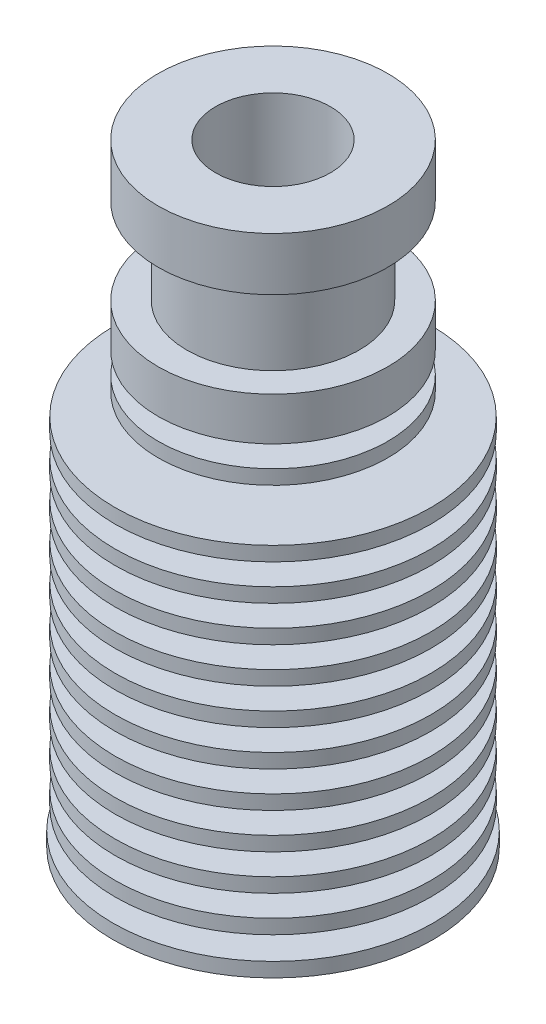
SolidWorks part; units mm, degrees
material "6061 Alloy"
ref_plane "Front Plane" through (0, 0, 0) normal (0, 0, 1) x (1, 0, 0)
ref_plane "Top Plane" through (0, 0, 0) normal (0, 1, 0) x (1, 0, 0)
ref_plane "Right Plane" through (0, 0, 0) normal (1, 0, 0) x (0, 0, -1)
sketch "Sketch1" plane through (0, 0, 0) normal (0, 0, 1) x (1, 0, 0)
  line L0 (0, 0) -> (0, -50000) construction
  line L1 (0, 0) -> (11.15, 0)
  line L2 (11.15, 0) -> (11.15, 1)
  line L3 (8, 30) -> (3.5, 30)
  line L4 (8, 30) -> (8, 33)
  line L5 (8, 33) -> (6, 33)
  line L6 (6, 33) -> (6, 39)
  line L7 (6, 39) -> (8, 39)
  line L8 (8, 39) -> (8, 42.7)
  line L9 (8, 42.7) -> (0, 42.7)
  line L10 (0, 42.7) -> (0, 0)
  line L12 (11, 1) -> (11, 26)
  line L13 (3.5, 26) -> (11, 26)
  line L14 (3.5, 27.5) -> (8, 27.5)
  line L15 (8, 27.5) -> (8, 28.5)
  line L16 (8, 28.5) -> (3.5, 28.5)
  line L17 (3.5, 28.5) -> (3.5, 30)
  line L18 (3.5, 27.5) -> (3.5, 26)
  line L20 (11.15, 1) -> (11, 1)
  dimension "D1" = 22.3
  dimension "D2" = 16
  dimension "D3" = 12
  dimension "D4" = 16
  dimension "D5" = 3.7
  dimension "D6" = 6
  dimension "D7" = 3
  dimension "D8" = 42.7
  dimension "D9" = 26
  dimension "D10" = 1.5
  dimension "D11" = 1
  dimension "D12" = 7
  dimension "D13" = 22
  dimension "D14" = 1
revolve "Revolve1" add sketch "Sketch1" angle 360 about L0 region at (4.9396, 19.0164, 0)
sketch "Sketch2" plane through (0, 0, 0) normal (0, 0, 1) x (1, 0, 0)
  line L0 (11, 1) -> (11, 26) construction
  line L3 (11, 1) -> (6, 1)
  line L4 (6, 1) -> (6, 2.5)
  line L5 (6, 2.5) -> (11, 2.5)
  line L6 (0, 0) -> (0, 26) construction
  line L7 (11.15, 26) -> (-11.15, 26) construction
  line L8 (11, 2.5) -> (11, 1)
  dimension "D1" = 2.5
  dimension "D3" = 12
revolve "Cut-Revolve1" cut sketch "Sketch2" angle 360 about L6 region at (8.5, 1.75, 0)
pattern_linear "LPattern1" count 10 spacing 2.5 along (0, 1, 0) of "Cut-Revolve1"
sketch "Sketch3" plane through (0, 0, 0) normal (0, 0, 1) x (1, 0, 0)
  line L0 (0, 42.7) -> (0, 0)
  line L1 (8, 42.7) -> (-8, 42.7) construction
  line L2 (0, 0) -> (2.1, 0)
  line L3 (-11.15, 0) -> (11.15, 0) construction
  line L4 (2.1, 0) -> (2.1, 34.3)
  line L6 (4, 36.2) -> (4, 42.7)
  line L7 (4, 42.7) -> (0, 42.7)
  line L8 (4, 36.2) -> (2.1, 34.3)
  dimension "D1" = 4
  dimension "D2" = 2.1
  dimension "D3" = 6.5
  dimension "D4" = 45
revolve "Cut-Revolve2" cut sketch "Sketch3" angle 360 about L0
hole_wizard "M7x1.0 Tapped Hole1" positions "Sketch5" profile "Sketch4" tap size "M7x1.0" standard "ANSI Metric"
sketch "Sketch5" plane through (0, 0, 0) normal (0, -1, 0) x (-1, 0, 0)
  point P0 (0, 0)
sketch "Sketch4" plane through (0, 0, 0) normal (1, 0, 0) x (0, 0, -1)
  line L0 (0, 0) -> (0, 16.9026)
  line L1 (0, 16.9026) -> (3, 15.1)
  line L2 (3, 15.1) -> (3, 0)
  line L5 (3, 0) -> (0, 0)
  line L10 (0, 16.9026) -> (-3, 15.1) construction
  line L11 (0, -6.35) -> (0, 107.95) construction
  dimension "Tap Drill Dia." = 6
  dimension "Tap Drill Depth" = 15.1
  dimension "Drill Angle" = 118
cosmetic thread "Hole Thread1" parameters "D1"=14, "D2"=7
